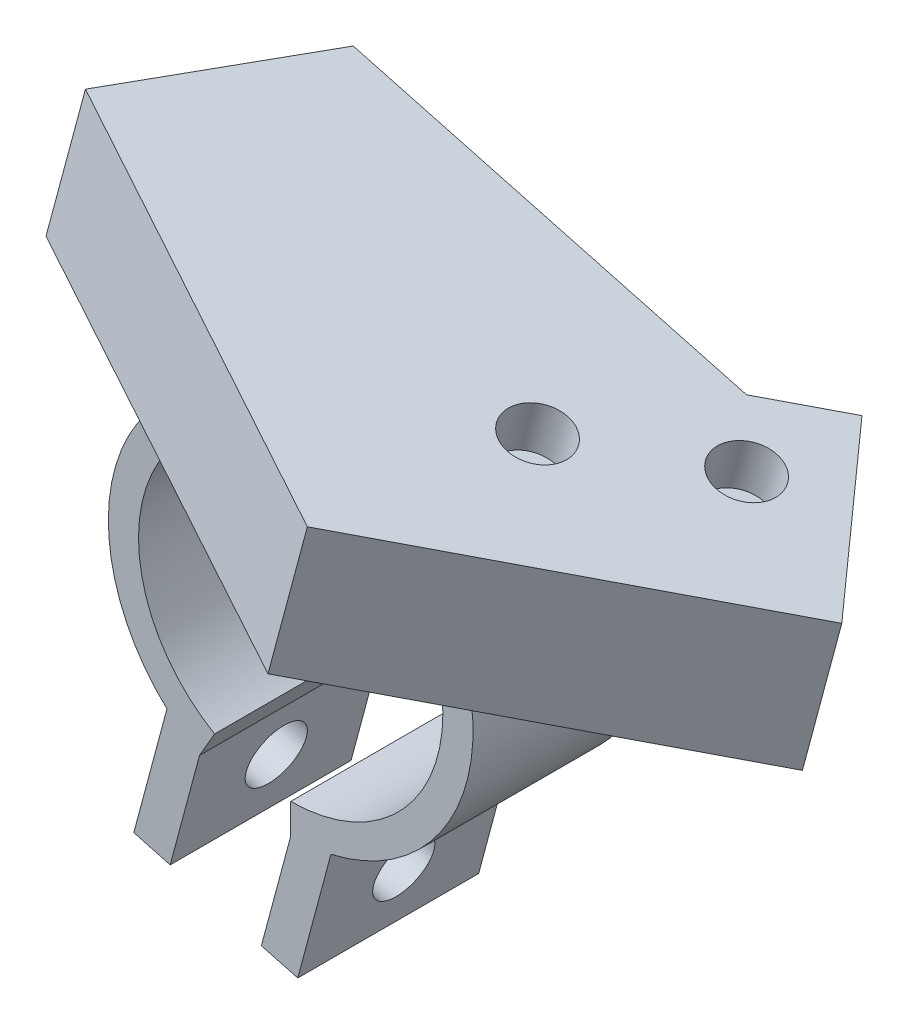
SolidWorks part; units mm, degrees
ref_plane "Front Plane" through (0, 0, 0) normal (0, 0, 1) x (1, 0, 0)
ref_plane "Top Plane" through (0, 0, 0) normal (0, 1, 0) x (1, 0, 0)
ref_plane "Right Plane" through (0, 0, 0) normal (1, 0, 0) x (0, 0, -1)
sketch "Sketch1" plane through (0, 0, 0) normal (0, 0, 1) x (1, 0, 0)
  circle A0 centre (0, 0) radius 20.193
  circle A1 centre (0, 0) radius 20.193 construction
  circle A2 centre (0, 0) radius 24.193
  dimension "D1" = 4
extrude "Boss-Extrude1" add sketch "Sketch1" along normal blind 24
sketch "Sketch2" plane through (0, 0, 24) normal (0, 0, 1) x (1, 0, 0)
  line L0 (0, -24.193) -> (-5.8342, -24.8953)
  line L1 (-5.8342, -24.8953) -> (-12.0965, -20.9518)
  line L2 (0, -24.193) -> (0, 0)
  line L3 (-12.0965, -20.9518) -> (0, 0)
  circle A0 centre (0, 0) radius 24.193 construction
  dimension "D1" = 7.4005
  dimension "D2" = 5.8342
  dimension "D3" = 30
extrude "Cut-Extrude1" cut sketch "Sketch2" against normal blind 24
sketch "Sketch3" plane through (0, 0, 24) normal (0, 0, 1) x (1, 0, 0)
  line L0 (-12.0965, -20.9518) -> (-15.99, -35.4826)
  line L1 (-15.99, -35.4826) -> (-20.8197, -34.1885)
  line L2 (-20.8197, -34.1885) -> (-16.4197, -17.7678)
  line L3 (-12.0965, -20.9518) -> (-16.4197, -17.7678)
  line L4 (0, -24.193) -> (5.336, -23.5972)
  line L5 (5.336, -23.5972) -> (0.9361, -40.0179)
  line L6 (0.9361, -40.0179) -> (-3.8935, -38.7238)
  line L7 (-3.8935, -38.7238) -> (0, -24.193)
  line L8 (-3.8935, -38.7238) -> (-15.99, -35.4826)
  line L9 (0, -24.193) -> (-12.0965, -20.9518)
  arc A0 (0, -24.193) -> (-12.0965, -20.9518) centre (0, 0) ccw construction
  arc M6 (0, -24.193) -> (-12.0965, -20.9518) centre (0, 0) ccw
  dimension "D1" = 17
  dimension "D2" = 5
extrude "Boss-Extrude2" add sketch "Sketch3" against normal blind 24 contours L2 L1 L0 M6 | L7 L6 L5 M6 region at (-16.3921, -27.1264, 24) region at (0.6327, -31.6882, 24)
sketch "Sketch4" plane through (-10.8779, 2.9147, 0) normal (-0.9659, 0.2588, 0) x (0, 0, 1)
  line L0 (12, -38.4121) -> (12, -30.4121)
  line L1 (0, -38.4121) -> (24, -38.4121) construction
  circle A0 centre (12, -30.4121) radius 4
  dimension "D2" = 8
  dimension "D1" = 8
extrude "Cut-Extrude2" cut sketch "Sketch4" against normal blind 24 contours A0 region at (-19.4605, -29.1159, 14.7484)
sketch "Sketch6" plane through (7.7901, 29.0729, 0) normal (-0.2588, -0.9659, 0) x (0.9659, -0.2588, 0)
  line L0 (-27.2706, 0) -> (-37.7263, 25.4348)
  line L2 (-37.7263, 25.4348) -> (15.3504, 47.2536)
  line L3 (15.3504, 47.2536) -> (53.361, 13.0569)
  line L4 (53.361, 13.0569) -> (34.9683, -7.3871)
  line L6 (34.9683, -7.3871) -> (9.8128, 15.2443)
  line L7 (9.8128, 15.2443) -> (-27.2706, 0)
  line L8 (11.2616, 0) -> (6.2616, 0) construction
  line L9 (-27.2706, 0) -> (26.7573, 0)
  line L11 (-34.8748, 18.498) -> (13.8402, 38.5238)
  line L13 (13.8402, 38.5238) -> (48.3448, 7.4812)
  circle A0 centre (33.9714, 6.9611) radius 4
  circle A1 centre (19.1031, 20.3376) radius 4
  line M37 (-59.6469, -13.3093) -> (9.8128, 15.2443)
  line M38 (9.8128, 15.2443) -> (95.193, -61.5692)
  line M50 (117.9188, -55.1119) -> (13.8402, 38.5238)
  line M51 (13.8402, 38.5238) -> (-92.8887, -5.3504)
  dimension "D5" = 8
  dimension "D6" = 8
  dimension "D9" = 20
  dimension "D2" = 33.8375
  dimension "D3" = 27.5
  dimension "D4" = 27.5
  dimension "D7" = 7.5
  dimension "D8" = 37.0834
  dimension "D10" = 10
  dimension "D11" = 10.3375
  dimension "D12" = 20
  dimension "D13" = 20
  dimension "D14" = 8.7298
  dimension "D15" = 62.2389
  dimension "D16" = 11.0449
  dimension "D17" = 22.7926
  dimension "D18" = 52.6705
  dimension "D19" = 6.9368
  dimension "D20" = 10.5948
  dimension "D21" = 14.7509
  dimension "D22" = 43.4984
extrude "Boss-Extrude3" add sketch "Sketch6" along normal blind 9.2 and the other way blind 11 contours L9 M37 M38 | L4 L0 L6 A1 A0 M50 M51 M37 M38 | L4 L3 L2 L0 M51 M50 region at (13.7236, 27.483, 16.5873) region at (10.7843, 28.2706, 5.0814) region at (-26.3856, 38.2303, 22.3443)
extrude "Cut-Extrude4" cut sketch "Sketch6<5>" against normal blind 4.5 contours L4 L0 L6 A1 A0 M50 M51 M37 M38 | L9 M37 M38 region at (13.7236, 27.483, 16.5873) region at (10.7843, 28.2706, 5.0814)
sketch "Sketch6<5>" plane through (7.7901, 29.0729, 0) normal (-0.2588, -0.9659, 0) x (0.9659, -0.2588, 0) same geometry as "Sketch6"
